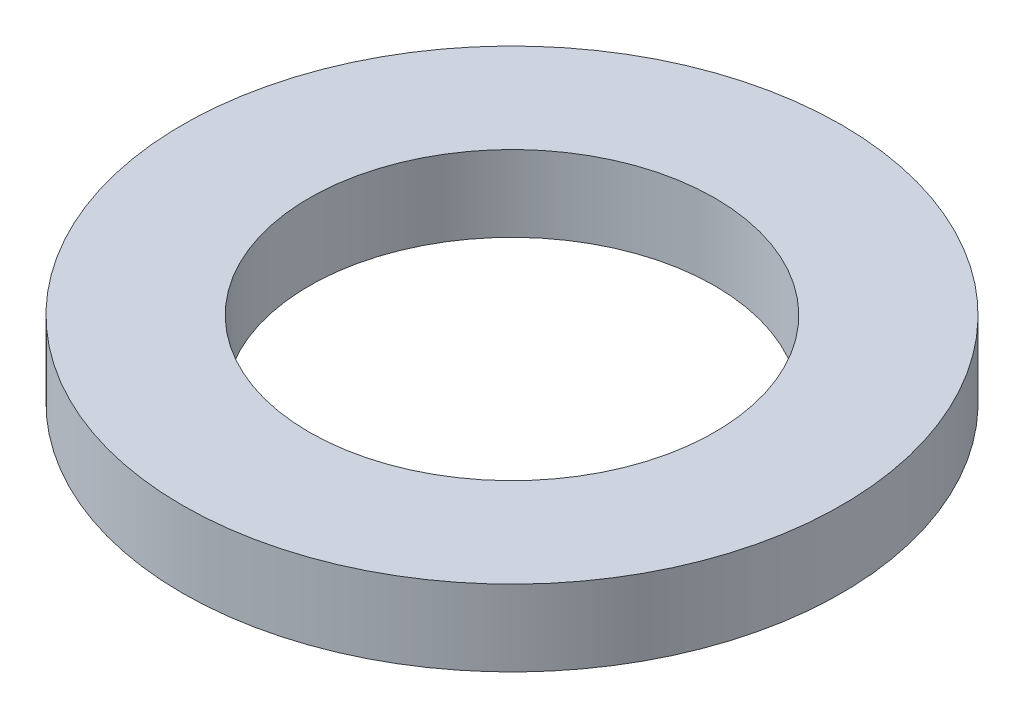
SolidWorks part; units mm, degrees
ref_plane "Front Plane" through (0, 0, 0) normal (0, 0, 1) x (1, 0, 0)
ref_plane "Top Plane" through (0, 0, 0) normal (0, 1, 0) x (1, 0, 0)
ref_plane "Right Plane" through (0, 0, 0) normal (1, 0, 0) x (0, 0, -1)
sketch "Sketch1" plane through (0, 0, 0) normal (0, 1, 0) x (1, 0, 0)
  circle A0 centre (0, 0) radius 65
  dimension "FLANGE_OD" = 130
extrude "Boss-Extrude1" add sketch "Sketch1" along normal blind 15
sketch "Sketch2" plane through (0, 0, 0) normal (0, 1, 0) x (1, 0, 0)
  circle A0 centre (0, 0) radius 40
  dimension "BORE_D" = 80
extrude "Cut-Extrude1" cut sketch "Sketch2" along normal through all
sketch "Sketch3" plane through (0, 15, 0) normal (0, 1, 0) x (1, 0, 0)
  circle A0 centre (0, 0) radius 27.0336 construction
  circle A1 centre (-27.0336, 0) radius 1.89
  dimension "BOLT_D" = 3.7801
  dimension "BOLT_PCD" = 54.0672
extrude "Cut-Extrude2" cut sketch "Sketch3" against normal blind 10.0343 rebuild error yes
pattern_circular "CirPattern1" count 3 over 360 rebuild error yes
